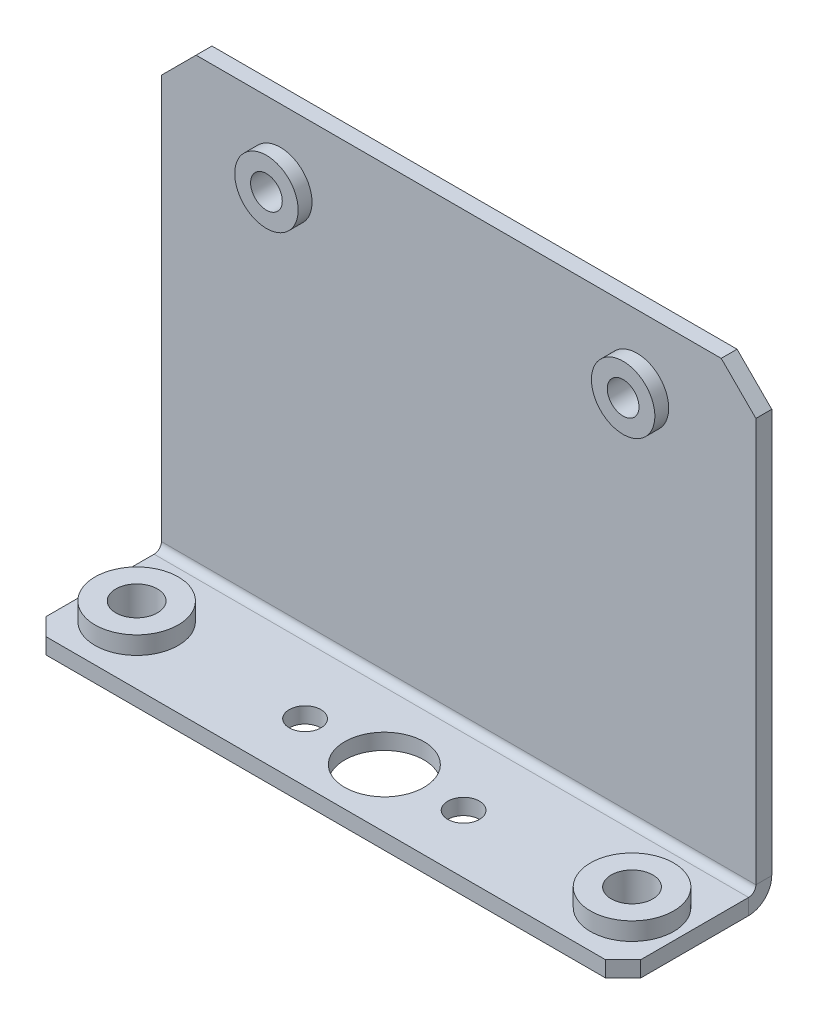
SolidWorks part; units mm, degrees
note: The reader was unsure of these and kept them because the rebuilt part matched: flange length of "边线-法兰1".
ref_plane "前视基准面" through (0, 0, 0) normal (0, 0, 1) x (1, 0, 0)
ref_plane "上视基准面" through (0, 0, 0) normal (0, 1, 0) x (1, 0, 0)
ref_plane "右视基准面" through (0, 0, 0) normal (1, 0, 0) x (0, 0, -1)
sketch "草图1" plane through (0, 0, 0) normal (0, 0, 1) x (1, 0, 0)
  line L0 (0, 60.1006) -> (0, -50.2728) construction
  line L1 (-26.5, 45) -> (26.5, 45)
  line L2 (-30, 41.5) -> (-30, 0)
  line L3 (-30, 0) -> (30, 0)
  line L4 (30, 41.5) -> (30, 0)
  line L5 (-30, 41.5) -> (-26.5, 45)
  line L6 (26.5, 45) -> (30, 41.5)
  dimension "D1" = 45
  dimension "D2" = 60
sheet metal parameters "钣金1" thickness 1.6 parameters "D1"=0.7366
base flange "基体-法兰1" sketch "草图1" thickness 1.6 reverse thickness direction no parameters "D1"=0.7366
edge flange "边线-法兰1" sketch "草图7" flange angle 90 flange length 15 flange position material outside bend radius 0.7366 thickness 1.6 relief rectangular parameters "D6"=10
sketch "草图7" plane through (0, 0, 0) normal (0, -1, 0) x (1, 0, 0)
  line L2 (-30, 0) -> (-30, 13.4)
  line L3 (-30, 13.4) -> (30, 13.4)
  line L4 (30, 13.4) -> (30, 0)
  line L5 (-30, 0) -> (30, 0) construction
  line L6 (-30, 0) -> (30, 0)
bend "边线折弯1" bend radius 0.7366 bend angle 90 parameters "D5"=1
sketch "草图8" plane through (0, 0, 0) normal (0, 1, 0) x (1, 0, 0)
  line L0 (-30, -11.6225) -> (-28.2225, -13.4)
  line L1 (-30, 0) -> (-30, -13.4) construction
  line L2 (30, -13.4) -> (-30, -13.4) construction
  line L3 (-30, -11.6225) -> (-30, -13.4)
  line L4 (-30, -13.4) -> (-28.2225, -13.4)
  line L5 (28.2225, -13.4) -> (30, -13.4)
  line L6 (30, -11.6225) -> (28.2225, -13.4)
  line L7 (30, -0.7366) -> (30, -13.4) construction
  line L8 (30, -13.4) -> (30, -11.6225)
  line L10 (-36.2942, -7.5) -> (36.3364, -7.5) construction
  dimension "D1" = 7.5
extrude "切除-拉伸1" cut sketch "草图8" against normal through all normal cut yes
sketch "草图9" plane through (0, 0, 0) normal (0, 1, 0) x (1, 0, 0)
  line L0 (-32.6904, -7.5) -> (31.4706, -7.5) construction
  line L1 (0, 4.201) -> (0, -15.3245) construction
  line L2 (-30, -11.6225) -> (-30, -0.7366) construction
  circle A0 centre (-25, -7.5) radius 4.2
  circle A1 centre (-8, -7.5) radius 1.6
  circle A2 centre (0, -7.5) radius 4
  circle A3 centre (8, -7.5) radius 1.6
  circle A4 centre (25, -7.5) radius 4.2
  circle A5 centre (-25, -7.5) radius 2.1
  circle A6 centre (25, -7.5) radius 2.1
  dimension "D4" = 8.4
  dimension "D5" = 3.2
  dimension "D6" = 8
  dimension "D7" = 4.2
  dimension "D1" = 7.5
  dimension "D2" = 5
  dimension "D3" = 22
extrude "切除-拉伸3" cut sketch "草图9" against normal blind 10 contours A5 | A1 | A2 | A6 | A3 normal cut yes
sketch "草图10" plane through (0, 0, 0) normal (0, 1, 0) x (1, 0, 0)
  line L0 (0, 4.1493) -> (0, -19.0333) construction
  circle A0 centre (-25, -7.5) radius 4.2
  circle A1 centre (-25, -7.5) radius 2.1
  circle A2 centre (-25, -7.5) radius 2.1
  circle A3 centre (25, -7.5) radius 4.2
  circle A4 centre (25, -7.5) radius 2.1
  dimension "D2" = 8.4
  dimension "D1" = 0
extrude "凸台-拉伸2" add sketch "草图10" along normal blind 1.8
sketch "草图11" plane through (0, 0, 0) normal (0, 0, 1) x (1, 0, 0)
  line L0 (-30, 41.5) -> (-30, 0.7366) construction
  line L1 (26.5, 45) -> (-26.5, 45) construction
  line L2 (0, -5.8937) -> (0, 58.7359) construction
  circle A0 centre (-18, 38) radius 3.2
  circle A1 centre (18, 38) radius 3.2
  dimension "D3" = 6.4
  dimension "D1" = 12
  dimension "D2" = 7
extrude "凸台-拉伸3" add sketch "草图11" along normal blind 1.4
sketch "草图12" plane through (0, 0, 1.4) normal (0, 0, 1) x (1, 0, 0)
  line L0 (-30, 41.5) -> (-30, 0.7366) construction
  line L2 (26.5, 45) -> (-26.5, 45) construction
  line L3 (0, -4.1274) -> (0, 47.842) construction
  circle A0 centre (-18, 38) radius 1.6
  circle A4 centre (18, 38) radius 1.6
  dimension "D3" = 3.2
  dimension "D1" = 12
  dimension "D2" = 7
extrude "切除-拉伸4" cut sketch "草图12" against normal through all normal cut yes
flat pattern "平板型式1" [suppressed]
sketch "折弯-线1" plane through (0, 0, 0) normal (0, 1, 0) x (-1, 0, 0)
sketch3d "边界框1" [suppressed]
  line L0 (60, 0, 0) -> (0, 0, 0) construction
  line L1 (60, 45, 0) -> (0, 45, 0) construction
  line L2 (60, 0, 0) -> (60, 45, 0) construction
  line L3 (0, 0, 0) -> (0, 45, 0) construction
bend of the flat pattern "展开-<边线折弯1>1"
